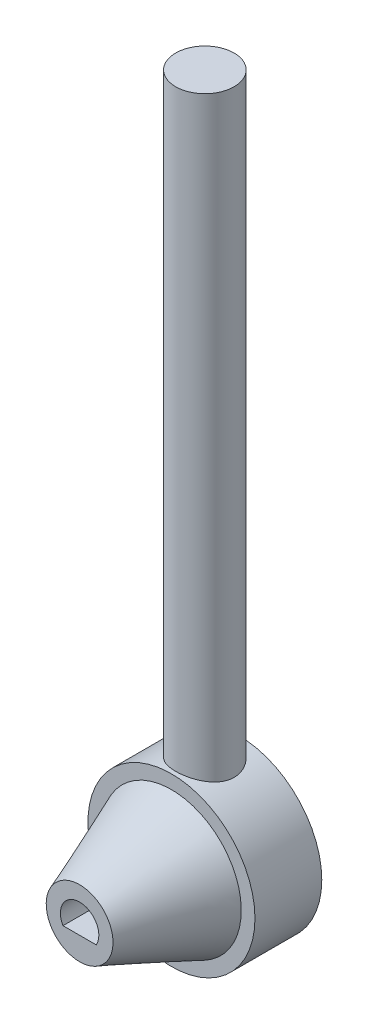
SolidWorks part; units mm, degrees
ref_plane "Front Plane" through (0, 0, 0) normal (0, 0, 1) x (1, 0, 0)
ref_plane "Top Plane" through (0, 0, 0) normal (0, 1, 0) x (1, 0, 0)
ref_plane "Right Plane" through (0, 0, 0) normal (1, 0, 0) x (0, 0, -1)
sketch "Sketch1" plane through (0, 0, 0) normal (0, 1, 0) x (1, 0, 0)
  circle A0 centre (0, 0) radius 3.5
extrude "Boss-Extrude1" add sketch "Sketch1" along normal blind 90
sketch "Sketch4" plane through (0, 0, 0) normal (0, 0, 1) x (1, 0, 0)
  circle A1 centre (0, 9) radius 10
ref_plane "Plane1" through (0, 0, 15) normal (0, 0, 1) x (1, 0, 0)
sketch "Sketch5" plane through (0, 0, 15) normal (0, 0, 1) x (1, 0, 0)
  line L2 (1.9922, 7.7506) -> (-1.9922, 7.7506)
  arc A0 (1.9922, 7.7506) -> (-1.9922, 7.7506) centre (0, 8.9001) ccw
sketch "Sketch6" plane through (0, 0, 15) normal (0, 0, 1) x (1, 0, 0)
  circle A0 centre (0, 9) radius 4
extrude "Boss-Extrude2" add sketch "Sketch4" along normal blind 4
extrude "Boss-Extrude3" add sketch "Sketch4<7>" against normal blind 4
sketch "Sketch4<7>" plane through (0, 0, 0) normal (0, 0, 1) x (1, 0, 0) same geometry as "Sketch4"
loft "Loft2" add profiles "Sketch4<8>", "Sketch6" connector at (-9.9735, 9.7282, 0) connector at (-3.8981, 8.1029, 15)
sketch "Sketch4<8>" plane through (0, 0, 0) normal (0, 0, 1) x (1, 0, 0) same geometry as "Sketch4"
extrude "Cut-Extrude3" cut sketch "Sketch5" against normal blind 6.5 contours A0 L2
